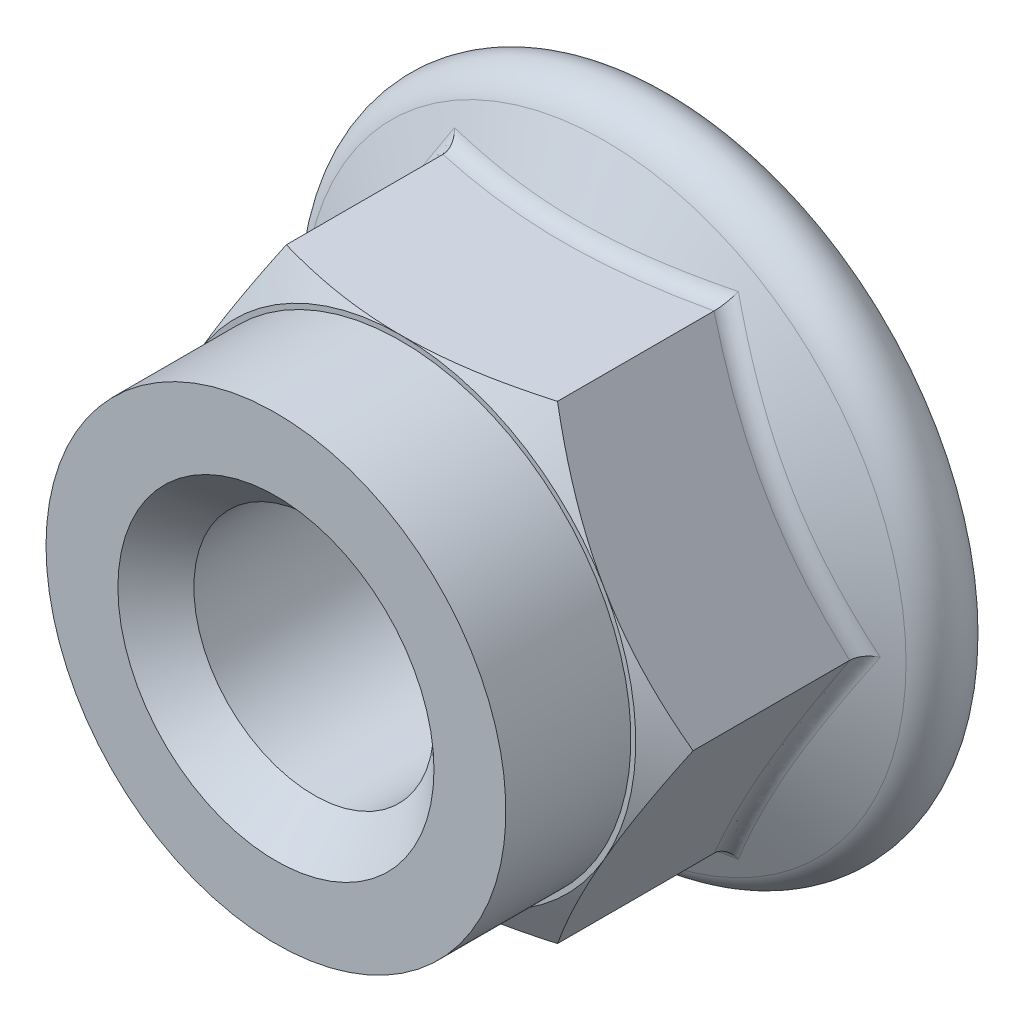
SolidWorks part; units mm, degrees
ref_plane "Front" through (0, 0, 0) normal (0, 0, 1) x (1, 0, 0)
ref_plane "Top" through (0, 0, 0) normal (0, 1, 0) x (1, 0, 0)
ref_plane "Right" through (0, 0, 0) normal (1, 0, 0) x (0, 0, -1)
sketch "Sketch1" plane through (0, 0, 0) normal (0, 0, 1) x (1, 0, 0)
  line L1 (3.7528, -6.5) -> (7.5056, 0)
  line L2 (7.5056, 0) -> (3.7528, 6.5)
  line L3 (3.7528, 6.5) -> (-3.7528, 6.5)
  line L4 (-3.7528, 6.5) -> (-7.5056, 0)
  line L5 (-7.5056, 0) -> (-3.7528, -6.5)
  line L6 (-3.7528, -6.5) -> (3.7528, -6.5)
  circle A0 centre (0, 0) radius 6.5 construction
  circle A1 centre (0, 0) radius 3.3235
  dimension "xd" = 6.647
  dimension "s" = 13
extrude "BaseNut" add sketch "Sketch1" against normal blind 7.64
cosmetic thread "ThreadCosmetic1" [suppressed] parameters "D2"=8
sketch "Sketch3" plane through (0.6779, 0, -16.6426) normal (0, 1, 0) x (0, 0, -1)
  line L0 (4.0352, 0.6779) -> (-19.0613, 0.6779) construction
  line L2 (-16.6426, 7.1779) -> (-16.0621, 8.1834)
  line L4 (-16.0621, 8.1834) -> (-16.6426, 8.1834)
  line L5 (-16.6426, 8.1834) -> (-16.6426, 7.1779)
  line L6 (-12.8226, 8.1834) -> (-12.8226, 14.238) construction
  line L8 (-9.0026, 8.1834) -> (-9.0026, 7.1779)
  line L9 (-9.5832, 8.1834) -> (-9.0026, 8.1834)
  line L10 (-9.0026, 7.1779) -> (-9.5832, 8.1834)
  line L12 (-9.0026, 8.1834) -> (-16.6426, 8.1834) construction
  dimension "D1" = 30
  dimension "sq" = 13
revolve "Double-Chamfer" cut sketch "Sketch3" angle 360 about L0
sketch "Sketch4" plane through (4.6827, 0, -16.7173) normal (0, 1, 0) x (0, 0, -1)
  line L0 (-21.7744, 4.6827) -> (9.7398, 4.6827) construction
  line L2 (-9.0773, 8.0062) -> (-9.0773, 12.5827)
  line L3 (-11.0789, 13.0264) -> (-13.4199, 8.0062)
  line L4 (-9.0773, 8.0062) -> (-16.7173, 8.0062) construction
  line L11 (-13.4199, 8.0062) -> (-9.0773, 8.0062)
  arc A0 (-9.0773, 12.5827) -> (-11.0789, 13.0264) centre (-10.1273, 12.5827) ccw
  dimension "D3" = 65
  dimension "m1" = 7.64
  dimension "dc" = 17.9
  dimension "dw" = 15.8
revolve "Flange" add sketch "Sketch4" angle 360 about L0
fillet "FlangeFillet" radius 0.48 6 edges at (-6.5022, 1.7379, -4.8861) (4.7562, 4.7621, -4.8861) (-4.7562, -4.7621, -4.8861) (6.5022, -1.7379, -4.8861)
sketch "Sketch5" plane through (-5.1971, 0, -15.1971) normal (0, 1, 0) x (0, 0, -1)
  line L0 (3.5984, -5.1971) -> (-23.9926, -5.1971) construction
  line L2 (-15.1971, -0.8221) -> (-15.1971, -1.8736) construction
  line L4 (-15.1971, -1.8736) -> (-14.1456, -1.8736) construction
  line L6 (-14.1456, -1.8736) -> (-15.1971, -0.8221) construction
  line L7 (-11.3771, -0.987) -> (-11.3771, -1.8736) construction
  line L8 (-8.6086, -1.8736) -> (-7.5571, -0.8221)
  line L9 (-7.5571, -1.8736) -> (-8.6086, -1.8736)
  line L10 (-7.5571, -0.8221) -> (-7.5571, -1.8736)
  line L15 (-7.5571, -1.8736) -> (-15.1971, -1.8736) construction
  dimension "da" = 8.75
  dimension "D2" = 45
revolve "EndChamfer1" cut sketch "Sketch5" angle 360 about L0
sketch "Sketch7" plane through (-3.0723, 10.3605, 0) normal (0, 0, 1) x (1, 0, 0)
  circle A1 centre (3.0723, -10.3605) radius 3.3235 construction
  circle A2 centre (3.0723, -10.3605) radius 6.365
  circle A3 centre (3.0723, -10.3605) radius 3.3235
  dimension "s1" = 12.73
extrude "TorqueElement" add sketch "Sketch7" along normal offset from surface (3.46 mm away) 11.1 up to face at (-4.375, 0, -7.64)
sketch "Sketch8" plane through (-6.8843, 0, -16.8843) normal (0, 1, 0) x (0, 0, -1)
  line L0 (3.9311, -6.8843) -> (-27.6997, -6.8843) construction
  line L2 (-20.3443, -2.5093) -> (-19.2928, -3.5608)
  line L5 (-19.2928, -3.5608) -> (-20.3443, -3.5608)
  line L6 (-20.3443, -3.5608) -> (-20.3443, -2.5093)
  line L7 (-20.3443, -0.5193) -> (-20.3443, -13.2493) construction
  line L9 (-10.2958, -3.5608) -> (-20.3443, -3.5608) construction
  dimension "D1" = 45
revolve "EndChamfer2" cut sketch "Sketch8" angle 360 about L0
sketch "Sketch9" plane through (0, 0, 0) normal (0, 1, 0) x (1, 0, 0)
  line L0 (0, 27.1353) -> (0, -11.1539) construction
  line L1 (2.647, 6.9267) -> (3.3235, 6.9267)
  line L2 (3.3235, 6.9267) -> (3.9094, 6.5885)
  line L3 (3.9094, 6.5885) -> (3.3235, 6.2502)
  line L4 (3.3235, 6.2502) -> (2.647, 6.2502)
  line L5 (2.647, 6.2502) -> (2.647, 6.9267)
  line L6 (-3.3235, 6.5885) -> (3.3235, 6.5885) construction
  dimension "D1" = 0.6765
  dimension "D2" = 6.647
revolve "Cut-Revolve10" [suppressed] cut sketch "Sketch9" angle 360 about L0
pattern_linear "LPattern10" [suppressed] count 13 spacing 0.8118 along (0, 0, 1) of bodies 107
equation "\"m1@Sketch4\" = \"m@BaseNut\""
equation "\"sq@Sketch3\" = \"s@Sketch1\""
equation "\"D2@Sketch9\" = \"xd@Sketch1\""
equation "\"D1@Sketch9\" = (  \"D2@ThreadCosmetic1\" - \"xd@Sketch1\" )  / 2"
equation "\"D3@LPattern10\" = \"D1@Sketch9\" * 1.2"
equation "\"D1@LPattern10\" =\"h@TorqueElement\" / \"D3@LPattern10\"-1"
